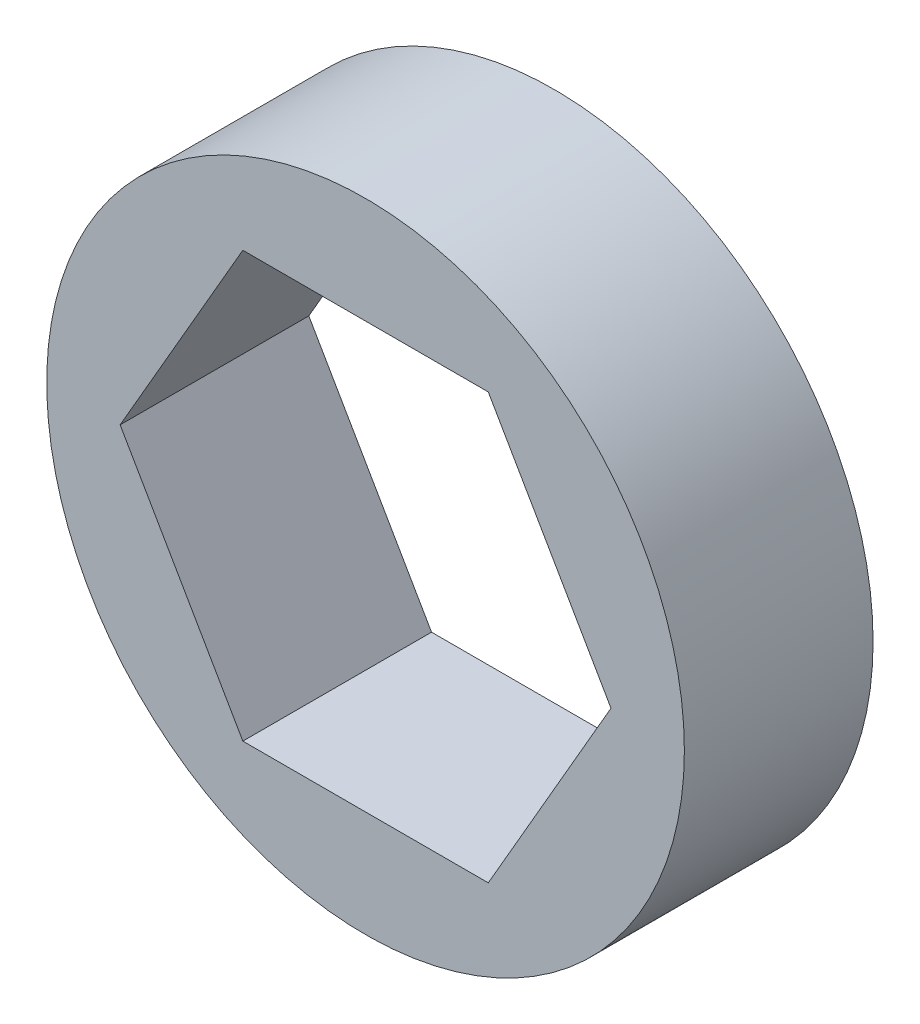
SolidWorks part; units mm, degrees
material "Nylon 101"
ref_plane "Front Plane" through (0, 0, 0) normal (0, 0, 1) x (1, 0, 0)
ref_plane "Top Plane" through (0, 0, 0) normal (0, 1, 0) x (1, 0, 0)
ref_plane "Right Plane" through (0, 0, 0) normal (1, 0, 0) x (0, 0, -1)
sketch "Sketch1" plane through (0, 0, 0) normal (0, 0, 1) x (1, 0, 0)
  line L1 (3.6662, 6.35) -> (-3.6662, 6.35)
  line L2 (-3.6662, 6.35) -> (-7.3323, 0)
  line L3 (-7.3323, 0) -> (-3.6662, -6.35)
  line L4 (-3.6662, -6.35) -> (3.6662, -6.35)
  line L5 (3.6662, -6.35) -> (7.3323, 0)
  line L6 (7.3323, 0) -> (3.6662, 6.35)
  circle A1 centre (0, 0) radius 9.525
  circle A2 centre (0, 0) radius 6.35 construction
  dimension "D1" = 19.05
  dimension ".5" = 12.7
extrude "Boss-Extrude1" add sketch "Sketch1" along normal blind 5.6375
